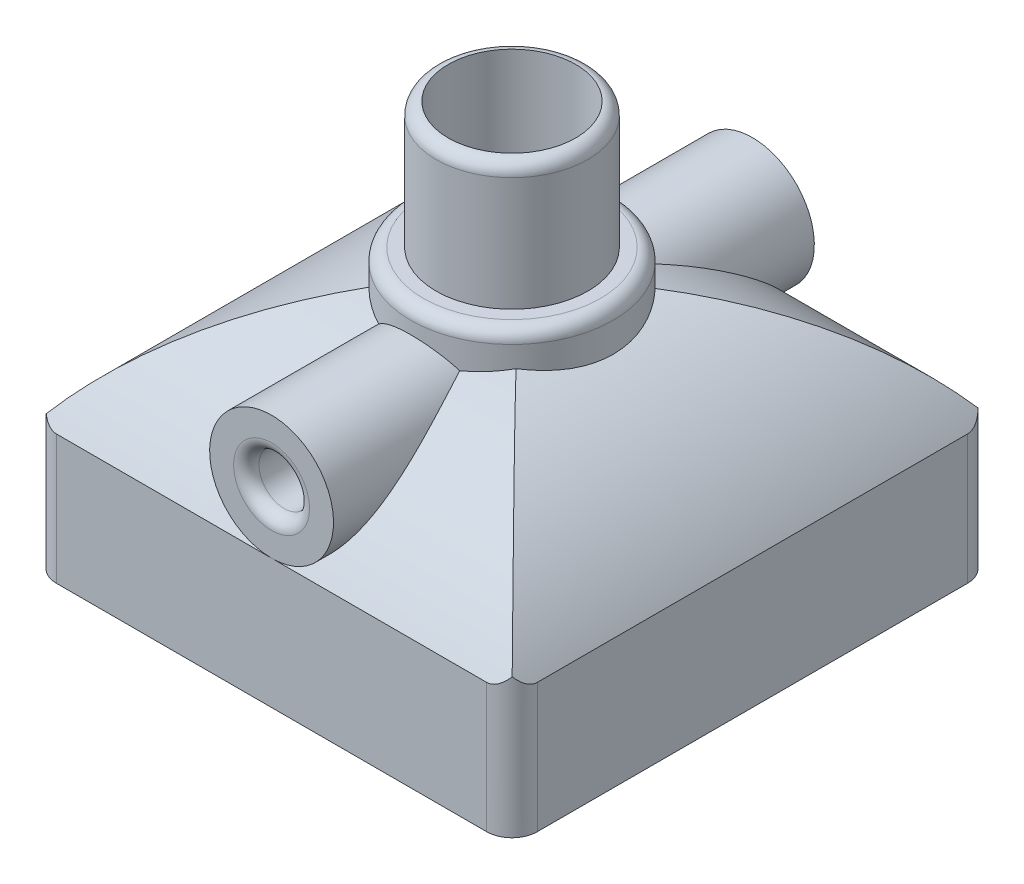
SolidWorks part; units mm, degrees
ref_plane "Front Plane" through (0, 0, 0) normal (0, 0, 1) x (1, 0, 0)
ref_plane "Top Plane" through (0, 0, 0) normal (0, 1, 0) x (1, 0, 0)
ref_plane "Right Plane" through (0, 0, 0) normal (1, 0, 0) x (0, 0, -1)
sketch "Sketch1" plane through (0, 0, 0) normal (0, 1, 0) x (1, 0, 0)
  line L1 (-9.5, 9.5) -> (9.5, 9.5)
  line L2 (-9.5, 9.5) -> (-9.5, -9.5)
  line L3 (-9.5, -9.5) -> (9.5, -9.5)
  line L4 (9.5, 9.5) -> (9.5, -9.5)
  line L5 (-9.5, 9.5) -> (9.5, -9.5) construction
  line L6 (-9.5, -9.5) -> (9.5, 9.5) construction
  point P0 (0, 0)
  dimension "D1" = 19
  dimension "D2" = 19
extrude "Boss-Extrude1" add sketch "Sketch1" along normal blind 10
ref_plane "Plane1" through (9.5, 10, -9.5) normal (0, -1, 0) x (-1, 0, 0)
sketch "Sketch6" plane through (0, 0, 9.5) normal (0, 0, 1) x (1, 0, 0)
  circle A0 centre (-0.044, 10.0226) radius 0.0226
  circle A2 centre (0.0917, -1.4428) radius 11.4662
  line M3 (9.5, 0) -> (9.5, 10)
  line M4 (9.5, 10) -> (-9.5, 10)
  line M5 (-9.5, 10) -> (-9.5, 0)
extrude "Cut-Extrude2" cut sketch "Sketch6" against normal through all contours A2 M3 M4 | A2 M4 M5 region at (7.2947, 8.6046, 9.5) region at (-7.2573, 8.5337, 9.5)
sketch "Sketch7" plane through (9.5, 0, 0) normal (1, 0, 0) x (0, 0, -1)
  line L0 (9.5, 10) -> (-9.5, 10) construction
  circle A0 centre (0, 10) radius 0.2675
  circle A2 centre (0, -1.6751) radius 11.6751
  line M1 (9.5, 5.1115) -> (-9.5, 5.1115)
  line M2 (-9.5, 5.1115) -> (-9.5, 0)
  line M3 (-9.5, 0) -> (9.5, 0)
  line M4 (9.5, 0) -> (9.5, 5.1115)
extrude "Cut-Extrude5" cut sketch "Sketch7" against normal through all flip side to cut contours A2 A0 M1 | M4 M1 M2 M3 region at (9.5, 7.1021, 0) region at (9.5, 2.5557, 0)
fillet "Fillet5" radius 1 1 edges at (-9.5, 2.42, -9.5)
fillet "Fillet6" radius 1 1 edges at (-9.5, 2.42, 9.5)
fillet "Fillet7" radius 1 2 edges at (9.5, 2.5557, -9.5) (9.5, 2.5557, 9.5)
sketch "Sketch8" plane through (0, 0, -9.5) normal (0, 0, -1) x (-1, 0, 0)
  line L0 (8.5, 5.1115) -> (-8.5, 5.1115) construction
  line L1 (-8.5, 0) -> (8.5, 0) construction
  circle A0 centre (0, 7.5588) radius 1
  circle A1 centre (0, 7.5588) radius 2.4473
  dimension "D1" = 2
  dimension "D2" = 7.5588
extrude "Boss-Extrude2" add sketch "Sketch8" against normal blind 19
ref_plane "Plane2" through (0, 10, 0) normal (0, 1, 0) x (1, 0, 0)
sketch "Sketch10" plane through (0, 10, 0) normal (0, 1, 0) x (1, 0, 0)
  circle A0 centre (0, 0) radius 4
  dimension "D1" = 8
extrude "Boss-Extrude4" add sketch "Sketch10" against normal blind 4
sketch "Sketch11" plane through (0, 10, 0) normal (0, 1, 0) x (1, 0, 0)
  circle A0 centre (0, 0) radius 4
extrude "Boss-Extrude5" add sketch "Sketch11" along normal blind 6
sketch "Sketch12" plane through (0, 16, 0) normal (0, 1, 0) x (1, 0, 0)
  circle A0 centre (0, 0) radius 4
  circle A1 centre (0, 0) radius 3
  dimension "D2" = 6
  dimension "D1" = 0
extrude "Cut-Extrude7" cut sketch "Sketch12" against normal blind 5
fillet "Fillet8" radius 0.5 1 edges at (0, 11, 4)
sketch "Sketch13" plane through (0, 16, 0) normal (0, 1, 0) x (1, 0, 0)
  circle A0 centre (0, 0) radius 3
  circle A1 centre (0, 0) radius 2.5199
extrude "Cut-Extrude8" cut sketch "Sketch13" against normal blind 5 flip side to cut
sketch "Sketch14" plane through (0, 0, 9.5) normal (0, 0, 1) x (1, 0, 0)
  circle A0 centre (0, 7.5588) radius 1
extrude "Cut-Extrude9" cut sketch "Sketch14" against normal blind 5
sketch "Sketch15" plane through (0, 0, -9.5) normal (0, 0, -1) x (-1, 0, 0)
  circle A0 centre (0, 7.5588) radius 1
extrude "Cut-Extrude10" cut sketch "Sketch15" against normal blind 5
fillet "Fillet10" radius 0.5 1 edges at (-1, 7.5588, -9.5)
fillet "Fillet11" radius 0.5 1 edges at (-1, 7.5588, 9.5)
fillet "Fillet12" radius 0.5 1 edges at (0, 16, 3)
